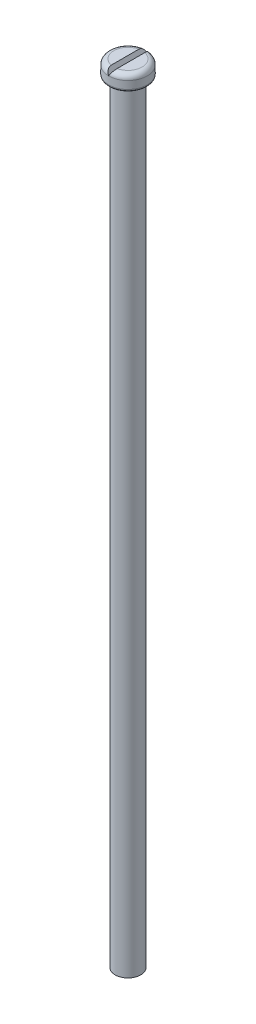
SolidWorks part; units mm, degrees
ref_plane "Front Plane" through (0, 0, 0) normal (0, 0, 1) x (1, 0, 0)
ref_plane "Top Plane" through (0, 0, 0) normal (0, 1, 0) x (1, 0, 0)
ref_plane "Right Plane" through (0, 0, 0) normal (1, 0, 0) x (0, 0, -1)
sketch "Sketch1" plane through (0, 0, 0) normal (0, 1, 0) x (1, 0, 0)
  circle A0 centre (0, 0) radius 2.5
  dimension "D1" = 5
extrude "Boss-Extrude1" add sketch "Sketch1" along normal blind 150
sketch "Sketch2" plane through (0, 150, 0) normal (0, 1, 0) x (1, 0, 0)
  circle A0 centre (0, 0) radius 3.75
  dimension "D1" = 7.5
extrude "Boss-Extrude2" add sketch "Sketch2" along normal blind 3
fillet "Fillet1" radius 1 1 edges at (0, 153, 3.75)
sketch "Sketch4" plane through (0, 0, 0) normal (0, 0, 1) x (1, 0, 0)
  line L0 (0, 0) -> (0, 152) construction
  line L1 (-3.75, 152) -> (3.75, 152) construction
  line L2 (0, 152) -> (-0.5774, 153)
  line L3 (2.75, 153) -> (-2.75, 153) construction
  line L4 (-0.5774, 153) -> (0.5774, 153)
  line L5 (0, 152) -> (0.5774, 153)
  point P10 (0, 153)
  dimension "D1" = 60
extrude "Cut-Extrude1" cut sketch "Sketch4" against normal blind 10 and the other way blind 10
fillet "Fillet2" radius 0.5 1 edges at (0, 150, 3.75)
